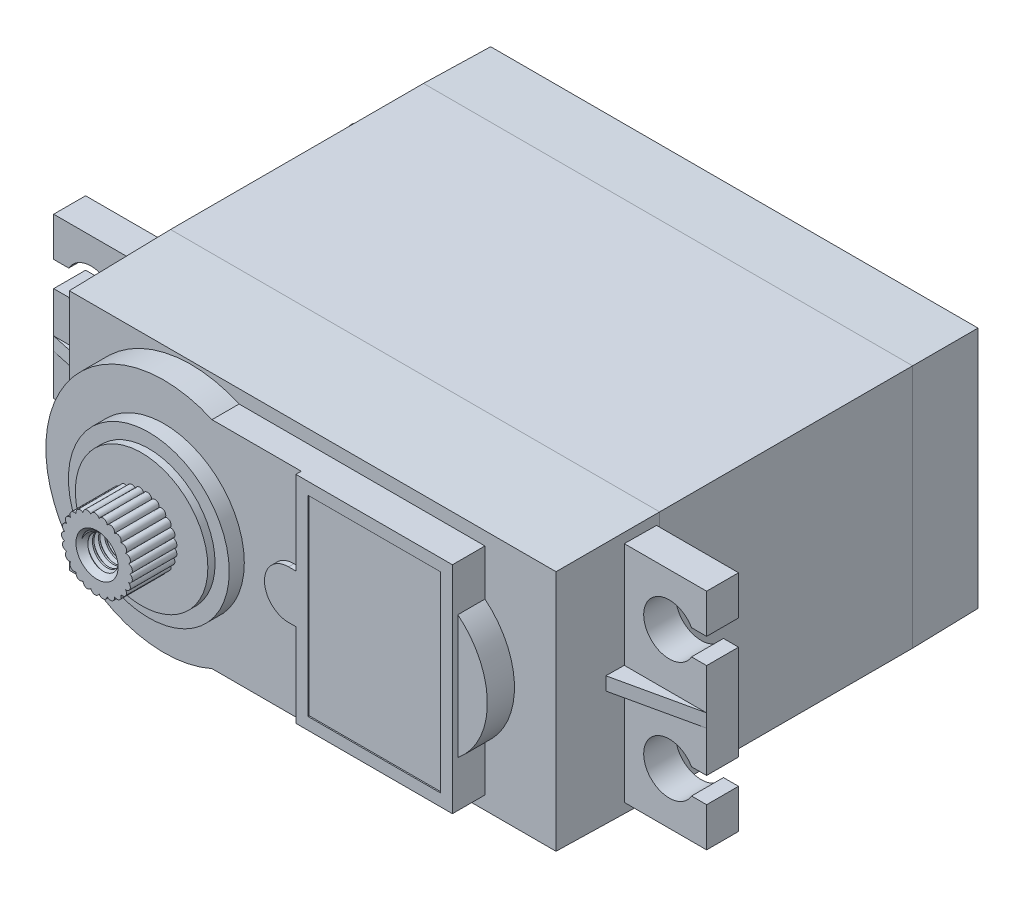
SolidWorks part; units mm, degrees
material "6061 Alloy"
ref_plane "Front Plane" through (0, 0, 0) normal (0, 0, 1) x (1, 0, 0)
ref_plane "Top Plane" through (0, 0, 0) normal (0, 1, 0) x (1, 0, 0)
ref_plane "Right Plane" through (0, 0, 0) normal (1, 0, 0) x (0, 0, -1)
sketch "Sketch1" plane through (0, 0, 0) normal (0, 0, 1) x (1, 0, 0)
  line L0 (0, 10.15) -> (0, -10.15) construction
  line L1 (-13.9, 5) -> (-13.9, -5) construction
  line L2 (30.4, 0) -> (-10.2, 0) construction
  line L3 (10.1, 10.15) -> (10.1, -10.15) construction
  line L4 (-10.2, 10.15) -> (30.4, 10.15)
  line L5 (-10.2, 10.15) -> (-10.2, -10.15)
  line L6 (-10.2, -10.15) -> (30.4, -10.15)
  line L7 (30.4, 10.15) -> (30.4, -10.15)
  line L8 (-17, 9.3) -> (37.2, 9.3)
  line L9 (-17, 9.3) -> (-17, 6.05)
  line L10 (-17, -9.3) -> (37.2, -9.3)
  line L11 (37.2, 9.3) -> (37.2, 6.05)
  line L12 (-13.9, -5) -> (34.1, -5) construction
  line L13 (34.1, -5) -> (34.1, 5) construction
  line L14 (34.1, 5) -> (-13.9, 5) construction
  line L15 (37.2, 3.95) -> (37.2, -3.95)
  line L16 (-17, 6.05) -> (-15.7475, 6.05)
  line L18 (-17, 3.95) -> (-15.7475, 3.95)
  line L20 (-17, -3.95) -> (-15.7475, -3.95)
  line L22 (-17, -6.05) -> (-15.7475, -6.05)
  line L24 (37.2, 6.05) -> (35.9475, 6.05)
  line L26 (37.2, 3.95) -> (35.9475, 3.95)
  line L28 (37.2, -3.95) -> (35.9475, -3.95)
  line L30 (37.2, -6.05) -> (35.9475, -6.05)
  line L32 (37.2, -6.05) -> (37.2, -9.3)
  line L33 (-17, 3.95) -> (-17, -3.95)
  line L34 (-17, -6.05) -> (-17, -9.3)
  arc A0 (-15.7475, 3.95) -> (-15.7475, 6.05) centre (-13.9, 5) ccw
  arc A1 (-15.7475, -6.05) -> (-15.7475, -3.95) centre (-13.9, -5) ccw
  arc A2 (35.9475, -3.95) -> (35.9475, -6.05) centre (34.1, -5) ccw
  arc A3 (35.9475, 6.05) -> (35.9475, 3.95) centre (34.1, 5) ccw
  dimension "D6" = 4.25
  dimension "D1" = 40.6
  dimension "D2" = 20.3
  dimension "D3" = 54.2
  dimension "D4" = 18.6
  dimension "D5" = 10.1
  dimension "D7" = 10
  dimension "D8" = 48
  dimension "D9" = 2.1
sketch "Sketch2" plane through (0, 0, 0) normal (0, 0, 1) x (1, 0, 0)
  line L0 (30.4, 0) -> (-10.2, 0) construction
  line L1 (3.9922, 8.95) -> (24.4, 8.95)
  line L3 (3.9922, -8.95) -> (24.4, -8.95)
  line L4 (24.4, 8.95) -> (24.4, 5.132)
  line L5 (24.4, -5.132) -> (24.4, -8.95)
  line L6 (10.1, 10.15) -> (10.1, -10.15) construction
  line L7 (0, 0) -> (26.85, 0) construction
  line L8 (11.4, 8.95) -> (11.4, 2)
  line L10 (10.8, 2) -> (11.4, 2)
  line L12 (10.8, -2) -> (11.4, -2)
  line L14 (11.4, -2) -> (11.4, -8.95)
  line L15 (24.4, 5.132) -> (24.4, -5.132)
  line L16 (12.4, 7.95) -> (23.4, 7.95)
  line L17 (12.4, 7.95) -> (12.4, -7.95)
  line L18 (12.4, -7.95) -> (23.4, -7.95)
  line L19 (23.4, 7.95) -> (23.4, -7.95)
  circle A0 centre (0, 0) radius 5.5
  circle A1 centre (0, 0) radius 6.675
  arc A2 (3.9922, 8.95) -> (3.9922, -8.95) centre (0, 0) ccw
  arc A3 (24.4, -5.132) -> (24.4, 5.132) centre (20.25, 0) ccw
  arc A5 (10.8, 2) -> (10.8, -2) centre (10.8, 0) ccw
  point P10 (-9.8, 0)
  point P26 (26.85, 0)
  dimension "D1" = 9.8
  dimension "D2" = 13.35
  dimension "D3" = 11
  dimension "D7" = 2
  dimension "D8" = 0.6
  dimension "D10" = 6.6
  dimension "D4" = 17.9
  dimension "D5" = 14.3
  dimension "D6" = 13
  dimension "D9" = 2.45
  dimension "D11" = 1
  dimension "D12" = 1
  dimension "D13" = 1
sketch "Sketch3" plane through (0, 0, 0) normal (0, 0, 1) x (1, 0, 0)
  line L0 (30.4, 0) -> (-10.2, 0) construction
  line L1 (-2.6787, 0.3384) -> (0, 0) construction
  line L2 (0, 0) -> (-2.6787, -0.3384) construction
  arc A1 (-2.6787, 0.3384) -> (-2.6787, -0.3384) centre (-2.6033, 0) ccw
  arc A2 (-2.5104, 0.9939) -> (-2.6787, 0.3384) centre (-2.5215, 0.6474) ccw
  arc A3 (-2.1843, 1.587) -> (-2.5104, 0.9939) centre (-2.2813, 1.2541) ccw
  arc A4 (-1.721, 2.0804) -> (-2.1843, 1.587) centre (-1.8977, 1.7821) ccw
  arc A5 (-1.1496, 2.443) -> (-1.721, 2.0804) centre (-1.3949, 2.198) ccw
  arc A6 (-0.5059, 2.6522) -> (-1.1496, 2.443) centre (-0.8045, 2.4759) ccw
  arc A7 (0.1695, 2.6947) -> (-0.5059, 2.6522) centre (-0.1635, 2.5982) ccw
  arc A8 (0.8343, 2.5679) -> (0.1695, 2.6947) centre (0.4878, 2.5572) ccw
  arc A9 (1.4467, 2.2797) -> (0.8343, 2.5679) centre (1.1084, 2.3555) ccw
  arc A10 (1.9682, 1.8483) -> (1.4467, 2.2797) centre (1.6594, 2.0059) ccw
  arc A11 (2.366, 1.3007) -> (1.9682, 1.8483) centre (2.1061, 1.5302) ccw
  arc A12 (2.6152, 0.6715) -> (2.366, 1.3007) centre (2.4205, 0.9583) ccw
  arc A13 (2.7, 0) -> (2.6152, 0.6715) centre (2.5828, 0.3263) ccw
  arc A14 (2.6152, -0.6715) -> (2.7, 0) centre (2.5828, -0.3263) ccw
  arc A15 (2.366, -1.3007) -> (2.6152, -0.6715) centre (2.4205, -0.9583) ccw
  arc A16 (1.9682, -1.8483) -> (2.366, -1.3007) centre (2.1061, -1.5302) ccw
  arc A17 (1.4467, -2.2797) -> (1.9682, -1.8483) centre (1.6594, -2.0059) ccw
  arc A18 (0.8343, -2.5679) -> (1.4467, -2.2797) centre (1.1084, -2.3555) ccw
  arc A19 (0.1695, -2.6947) -> (0.8343, -2.5679) centre (0.4878, -2.5572) ccw
  arc A20 (-0.5059, -2.6522) -> (0.1695, -2.6947) centre (-0.1635, -2.5982) ccw
  arc A21 (-1.1496, -2.443) -> (-0.5059, -2.6522) centre (-0.8045, -2.4759) ccw
  arc A22 (-1.721, -2.0804) -> (-1.1496, -2.443) centre (-1.3949, -2.198) ccw
  arc A23 (-2.1843, -1.587) -> (-1.721, -2.0804) centre (-1.8977, -1.7821) ccw
  arc A24 (-2.5104, -0.9939) -> (-2.1843, -1.587) centre (-2.2813, -1.2541) ccw
  arc A25 (-2.6787, -0.3384) -> (-2.5104, -0.9939) centre (-2.5215, -0.6474) ccw
  circle A26 centre (0, 0) radius 1.25
  point P1 (-2.95, 0)
  point P83 (0, 0)
  dimension "D5" = 2.5
  dimension "D1" = 2.95
  dimension "D2" = 14.4
  dimension "D3" = 2.7
  dimension "D4" = 25
extrude "MainCase" add sketch "Sketch1" against normal blind 37 contours L5 L6 L7 L4
extrude "Flange" add sketch "Sketch1<3>" against normal blind 2.65 from offset 5.6 contours L10 L32 L30 A2 L28 L15 L26 A3 L24 L11 L8 L9 L16 A0 L18 L33 L20 A1 L22 L34 offset against normal yes
sketch "Sketch1<3>" plane through (0, 0, 0) normal (0, 0, 1) x (1, 0, 0) same geometry as "Sketch1"
extrude "TopFace" add sketch "Sketch2" along normal blind 2.25 contours L3 L5 A3 L4 L1 A2
extrude "Boss-Extrude4" add sketch "Sketch2<3>" along normal blind 3.5 contours A1
sketch "Sketch2<3>" plane through (0, 0, 0) normal (0, 0, 1) x (1, 0, 0) same geometry as "Sketch2"
extrude "Boss-Extrude5" add sketch "Sketch2<4>" along normal blind 4.1 contours A0
sketch "Sketch2<4>" plane through (0, 0, 0) normal (0, 0, 1) x (1, 0, 0) same geometry as "Sketch2"
extrude "Boss-Extrude6" add sketch "Sketch2<7>" along normal blind 2.7 contours A5 L7 L17 L16 L19 L15 L4 L1 L8 L10 | L7 A5 L12 L14 L3 L5 L15 L19 L18 L17 region at (17.9, 8.7701, 0) region at (11.5799, -5.475, 0)
sketch "Sketch2<7>" plane through (0, 0, 0) normal (0, 0, 1) x (1, 0, 0) same geometry as "Sketch2"
extrude "Boss-Extrude7" add sketch "Sketch2<8>" along normal blind 2.6 contours L17 L7 L19 L16 | L7 L17 L18 L19 region at (17.9, -3.975, 0) region at (17.9, 3.975, 0)
sketch "Sketch2<8>" plane through (0, 0, 0) normal (0, 0, 1) x (1, 0, 0) same geometry as "Sketch2"
extrude "Boss-Extrude9" add sketch "Sketch3" along normal blind 7.8 contours A1 A25 A24 A23 A22 A21 A20 A19 A18 A17 A16 A15 A14 A13 A12 A11 A10 A9 A8 A7 A6 A5 A4 A3 A2 A26 region at (-2.7767, 0.7129, 0)
extrude "Boss-Extrude10" add sketch "Sketch3<4>" along normal blind 3.7 contours A26 region at (0, 0, 0)
sketch "Sketch3<4>" plane through (0, 0, 0) normal (0, 0, 1) x (1, 0, 0) same geometry as "Sketch3"
sketch "Sketch7" plane through (0, 0, 0) normal (0, 1, 0) x (1, 0, 0)
  line L0 (-17, 5.6) -> (37.2, 5.6)
  line L1 (37.2, 5.6) -> (30.4, 4.1)
  line L2 (30.4, 4.1) -> (-10.2, 4.1)
  line L3 (-10.2, 4.1) -> (-17, 5.6)
  line L5 (30.4, 4.1) -> (30.4, 5.6) construction
  dimension "D1" = 1.5
extrude "Boss-Extrude11" add sketch "Sketch7" along normal blind 0.55 and the other way blind 0.55 contours L1 L2 L3 L0
chamfer "Chamfer1" distance 0.5 angle 45 1 edges at (1.25, 0, 7.8)
thread "Thread1" pitch 0.5 method cut profile "Thread Profile1" start angle 0, offset 1, length 4, pitch 0.5, diameter 2.5
ref_plane "Plane1" through (-1.25, 0, 8.3) normal (0, -1, 0) x (-1, 0, 0)
sketch "Thread Profile1" plane through (-1.25, 0, 8.3) normal (0, -1, 0) x (-1, 0, 0)
  line L0 (0, 0) -> (0, 0.5) construction
  line L1 (0, 0) -> (0.2706, 0.1562)
  line L2 (0.2706, 0.1562) -> (0.2706, 0.2187)
  line L3 (0.2706, 0.2187) -> (0, 0.375)
  line L4 (0.2706, 0.1875) -> (0, 0.1875) construction
  line L11 (0, 0) -> (0, 0.375)
  point P2 (0, 0)
  dimension "Pitch" = 0.5
  dimension "Profile_Angle" = 60
  dimension "Profile_Land" = 0.0625
  dimension "Profile_Height" = 0.2706
chamfer "Chamfer2" distance 7.5 distance2 0.1 4 edges at (-10.2, 0, -37) (10.1, -10.15, -37) (30.4, 0, -37) (10.1, 10.15, -37) first distance on face at (-10.2, 0, -5.8875) first distance on face at (10.1, -10.15, -18.5) first distance on face at (30.4, 0, -18.5) first distance on face at (10.1, 10.15, -18.5)
chamfer "Chamfer3" distance 2 angle 45 4 edges at (30.3, 0, -37) (10.1, 10.05, -37) (-10.1, 0, -37) (10.1, -10.05, -37) first distance on face at (30.35, 0, -33.25) first distance on face at (10.1, 10.1, -33.25) first distance on face at (-10.15, 0, -33.25) first distance on face at (10.1, -10.1, -33.25)
chamfer "Chamfer4" distance 8.5 distance2 0.1 4 edges at (10.1, 10.15, 0) (30.4, 0, 0) (-10.2, 0, 0) (10.1, -10.15, 0) first distance on face at (10.1, 10.15, -14.75) first distance on face at (30.4, 0, -14.75) first distance on face at (-10.2, 0, -5.8875) first distance on face at (10.1, -10.15, -14.75)
sketch "Sketch8" plane through (-10.2, 0, 0) normal (-1, 0, 0) x (0, 0, 1)
  line L0 (0, 0) -> (-37, 0) construction
  line L1 (-31.5, 3.2) -> (-31.5, -3.2) construction
  line L2 (-37, -8.0228) -> (-37, 8.0228) construction
  line L3 (-30, 3.2) -> (-33, 3.2)
  line L4 (-29.5, 2.7) -> (-29.5, -2.7)
  line L5 (-30, -3.2) -> (-33, -3.2)
  line L6 (-33.5, 2.7) -> (-33.5, -2.7)
  arc A0 (-29.5, -2.7) -> (-30, -3.2) centre (-30, -2.7) cw
  arc A1 (-33, -3.2) -> (-33.5, -2.7) centre (-33, -2.7) cw
  arc A2 (-33, 3.2) -> (-33.5, 2.7) centre (-33, 2.7) ccw
  arc A3 (-30, 3.2) -> (-29.5, 2.7) centre (-30, 2.7) cw
  arc A4 (-31.692, 0.725) -> (-31.692, -0.725) centre (-31.5, 0) ccw
  arc A5 (-31.692, -0.725) -> (-31.308, -0.725) centre (-31.5, -1.45) ccw
  arc A6 (-31.308, 0.725) -> (-31.692, 0.725) centre (-31.5, 1.45) ccw
  arc A7 (-31.308, -0.725) -> (-31.308, 0.725) centre (-31.5, 0) ccw
  dimension "D4" = 0.5
  dimension "D5" = 1.5
  dimension "D6" = 2.9
  dimension "D1" = 5.5
  dimension "D2" = 4
  dimension "D3" = 6.4
extrude "Boss-Extrude12" add sketch "Sketch8" along normal blind 5 and the other way blind 1
extrude "Boss-Extrude13" add sketch "Sketch8<2>" along normal blind 8 contours A5 A7 A6 A4 region at (-10.2, 0, -31.5)
sketch "Sketch8<2>" plane through (-10.2, 0, 0) normal (-1, 0, 0) x (0, 0, 1) same geometry as "Sketch8"
chamfer "Chamfer5" distance 4 distance2 0.3 8 edges at (-15.2, -3.2, -31.5) (-15.2, -3.0536, -33.3536) (-15.2, 0, -33.5) (-15.2, 3.0536, -33.3536) (-15.2, 3.2, -31.5) (-15.2, 3.0536, -29.6464) (-15.2, 0, -29.5) (-15.2, -3.0536, -29.6464) first distance on face at (-12.6867, -3.2, -31.5) first distance on face at (-12.6747, -3.0018, -33.3018) first distance on face at (-12.6733, 0, -33.5) first distance on face at (-12.6747, 3.0018, -33.3018) first distance on face at (-12.6867, 3.2, -31.5) first distance on face at (-12.6987, 3.0018, -29.6982) first distance on face at (-12.7, 0, -29.5) first distance on face at (-12.6987, -3.0018, -29.6982)
